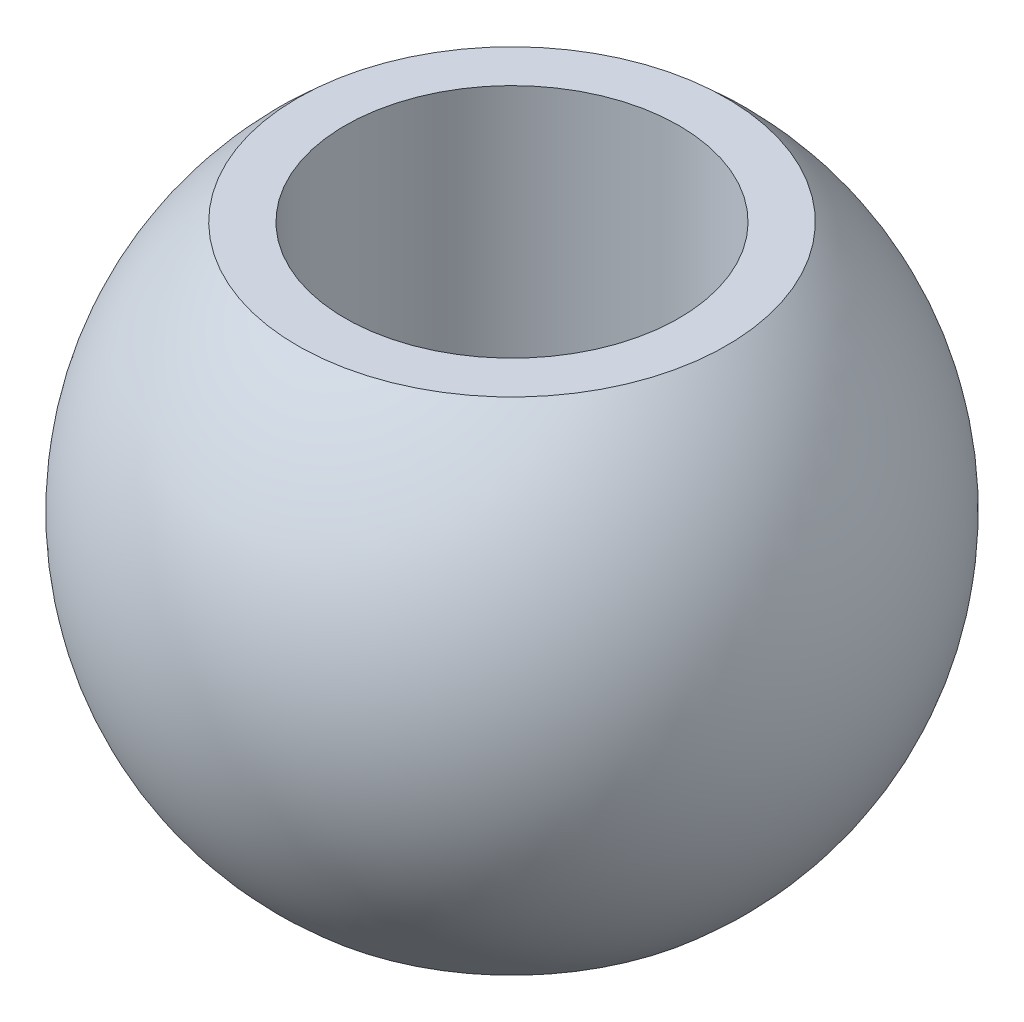
SolidWorks part; units mm, degrees
material "ABS PC"
ref_plane "Płaszczyzna przednia" through (0, 0, 0) normal (0, 0, 1) x (1, 0, 0)
ref_plane "Płaszczyzna górna" through (0, 0, 0) normal (0, 1, 0) x (1, 0, 0)
ref_plane "Płaszczyzna prawa" through (0, 0, 0) normal (1, 0, 0) x (0, 0, -1)
sketch "Szkic1" plane through (0, 0, 0) normal (0, 0, 1) x (1, 0, 0)
  line L0 (-5.1391, 6) -> (-4, 6)
  line L1 (-5.1391, -6) -> (-4, -6)
  line L2 (-4, 6) -> (-4, -6)
  line L3 (0, 0) -> (0, 10.4296) construction
  arc A0 (-5.1391, 6) -> (-5.1391, -6) centre (0, 0) ccw
  dimension "D1" = 15.8
  dimension "D2" = 6
  dimension "D3" = 6
  dimension "D4" = 4
revolve "Obrót1" add sketch "Szkic1" angle 360 about L3
